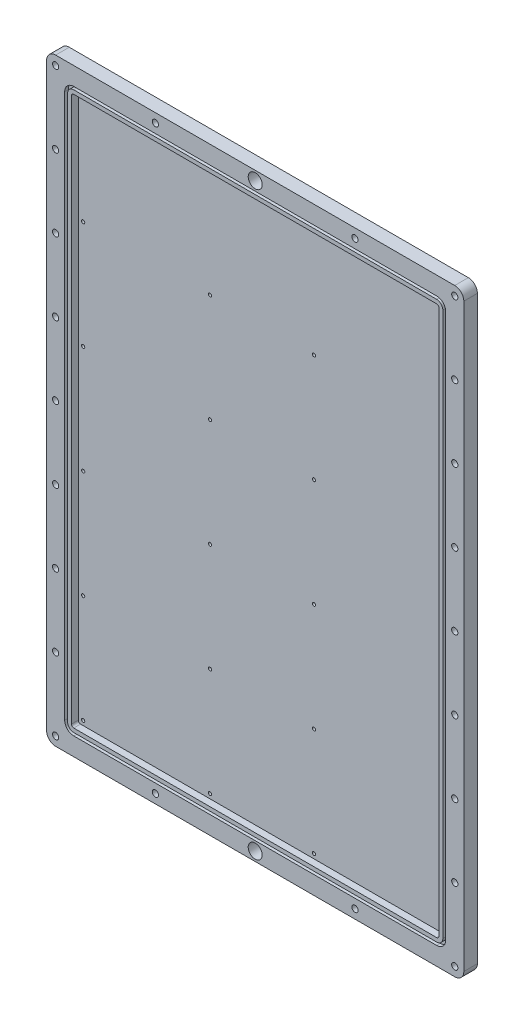
SolidWorks part; units mm, degrees
ref_plane "Front Plane" through (0, 0, 0) normal (0, 0, 1) x (1, 0, 0)
ref_plane "Top Plane" through (0, 0, 0) normal (0, 1, 0) x (1, 0, 0)
ref_plane "Right Plane" through (0, 0, 0) normal (1, 0, 0) x (0, 0, -1)
sketch "Sketch1" plane through (0, 0, 0) normal (0, 0, 1) x (1, 0, 0)
  line L1 (0, 0) -> (292.0492, 0)
  line L2 (0, 0) -> (0, 419.0492)
  line L3 (0, 419.0492) -> (292.0492, 419.0492)
  line L4 (292.0492, 0) -> (292.0492, 419.0492)
  dimension "D1" = 419.0492
  dimension "D2" = 292.0492
extrude "Boss-Extrude1" add sketch "Sketch1" along normal blind 9.525
sketch "Sketch4" plane through (0, 0, 9.525) normal (0, 0, 1) x (1, 0, 0)
  line L0 (91.477, 6.3246) -> (91.477, 0) construction
  line L1 (0, 0) -> (292.0492, 0) construction
  line L2 (6.3246, 94.9672) -> (0, 94.9672) construction
  line L4 (6.3246, 412.7246) -> (285.7246, 412.7246) construction
  line L5 (6.3246, 412.7246) -> (6.3246, 6.3246) construction
  line L6 (6.3246, 6.3246) -> (285.7246, 6.3246) construction
  line L7 (285.7246, 412.7246) -> (285.7246, 6.3246) construction
  line L11 (0, 419.0492) -> (0, 0) construction
  line L12 (285.7246, 110.613) -> (292.0492, 110.613) construction
  line L13 (292.0492, 0) -> (292.0492, 419.0492) construction
  line L14 (125.5626, 412.7246) -> (125.5626, 419.0492) construction
  line L15 (292.0492, 419.0492) -> (0, 419.0492) construction
  circle A0 centre (6.3246, 6.3246) radius 2.1844
  circle A1 centre (6.3246, 412.7246) radius 2.1844
  circle A2 centre (285.7246, 412.7246) radius 2.1844
  circle A3 centre (285.7246, 6.3246) radius 2.1844
  dimension "D5" = 4.3688
  dimension "D1" = 279.4
  dimension "D2" = 406.4
extrude "Cut-Extrude1" cut sketch "Sketch4" against normal through all
sketch "Sketch5" plane through (0, 0, 9.525) normal (0, 0, 1) x (1, 0, 0)
  line L0 (0, 209.5246) -> (12.6746, 209.5246) construction
  line L1 (19.0246, 406.3746) -> (273.0246, 406.3746)
  line L2 (12.6746, 400.0246) -> (12.6746, 19.0246)
  line L3 (19.0246, 12.6746) -> (273.0246, 12.6746)
  line L4 (279.3746, 400.0246) -> (279.3746, 19.0246)
  line L5 (0, 419.0492) -> (0, 0) construction
  line L6 (279.3746, 209.5246) -> (292.0492, 209.5246) construction
  line L8 (19.0246, 14.7066) -> (273.0246, 14.7066)
  line L9 (14.7066, 400.0246) -> (14.7066, 19.0246)
  line L10 (19.0246, 404.3426) -> (273.0246, 404.3426)
  line L11 (277.3426, 400.0246) -> (277.3426, 19.0246)
  line L12 (292.0492, 0) -> (292.0492, 419.0492) construction
  line L13 (146.0246, 12.6746) -> (146.0246, 0) construction
  line L14 (0, 0) -> (292.0492, 0) construction
  line L15 (146.0246, 406.3746) -> (146.0246, 419.0492) construction
  line L16 (292.0492, 419.0492) -> (0, 419.0492) construction
  arc A0 (273.0246, 12.6746) -> (279.3746, 19.0246) centre (273.0246, 19.0246) ccw
  arc A1 (12.6746, 19.0246) -> (19.0246, 12.6746) centre (19.0246, 19.0246) ccw
  arc A2 (273.0246, 406.3746) -> (279.3746, 400.0246) centre (273.0246, 400.0246) cw
  arc A3 (19.0246, 406.3746) -> (12.6746, 400.0246) centre (19.0246, 400.0246) ccw
  arc A4 (14.7066, 19.0246) -> (19.0246, 14.7066) centre (19.0246, 19.0246) ccw
  arc A5 (19.0246, 404.3426) -> (14.7066, 400.0246) centre (19.0246, 400.0246) ccw
  arc A6 (273.0246, 404.3426) -> (277.3426, 400.0246) centre (273.0246, 400.0246) cw
  arc A7 (273.0246, 14.7066) -> (277.3426, 19.0246) centre (273.0246, 19.0246) ccw
  dimension "D5" = 6.35
  dimension "D1" = 266.7
  dimension "D2" = 393.7
  dimension "D6" = 2.032
  dimension "D7" = 2.032
extrude "Cut-Extrude2" cut sketch "Sketch5" against normal blind 2.54 contours L1 A3 L2 A1 L3 A0 L4 A2 A7 L8 A4 L9 A5 L10 A6 L11 region at (146.0246, 405.8991, 9.525)
pattern_linear "LPattern3" count 4 spacing 69.85 along (1, 0, 0) of face at (8.509, 412.7246, 0) of face at (8.509, 6.3246, 0)
pattern_linear "LPattern4" count 8 spacing 50.8 along (0, -1, 0) of face at (8.509, 412.7246, 0) of face at (287.909, 412.7246, 0)
sketch "Sketch6" plane through (0, 0, 9.525) normal (0, 0, 1) x (1, 0, 0)
  line L4 (274.6121, 19.0246) -> (274.6121, 400.0246)
  line L5 (274.6121, 19.0246) -> (274.6121, 400.0246)
  line L6 (273.0246, 401.6121) -> (19.0246, 401.6121)
  line L7 (273.0246, 401.6121) -> (19.0246, 401.6121)
  line L8 (17.4371, 400.0246) -> (17.4371, 19.0246)
  line L9 (17.4371, 400.0246) -> (17.4371, 19.0246)
  line L10 (19.0246, 17.4371) -> (273.0246, 17.4371)
  line L11 (19.0246, 17.4371) -> (273.0246, 17.4371)
  arc A4 (273.0246, 17.4371) -> (274.6121, 19.0246) centre (273.0246, 19.0246) ccw
  arc A5 (273.0246, 17.4371) -> (274.6121, 19.0246) centre (273.0246, 19.0246) ccw
  arc A6 (274.6121, 400.0246) -> (273.0246, 401.6121) centre (273.0246, 400.0246) ccw
  arc A7 (274.6121, 400.0246) -> (273.0246, 401.6121) centre (273.0246, 400.0246) ccw
  arc A8 (19.0246, 401.6121) -> (17.4371, 400.0246) centre (19.0246, 400.0246) ccw
  arc A9 (19.0246, 401.6121) -> (17.4371, 400.0246) centre (19.0246, 400.0246) ccw
  arc A10 (17.4371, 19.0246) -> (19.0246, 17.4371) centre (19.0246, 19.0246) ccw
  arc A11 (17.4371, 19.0246) -> (19.0246, 17.4371) centre (19.0246, 19.0246) ccw
  dimension "D1" = 2.7305
extrude "Cut-Extrude3" cut sketch "Sketch6" against normal blind 4.7625
sketch "Sketch7" plane through (0, 0, 4.7625) normal (0, 0, 1) x (1, 0, 0)
  line L0 (273.0246, 401.6121) -> (19.0246, 401.6121) construction
  line L1 (20.8407, 398.4371) -> (271.2085, 398.4371) construction
  line L2 (20.8407, 398.4371) -> (20.8407, 20.6121) construction
  line L3 (20.8407, 20.6121) -> (271.2085, 20.6121) construction
  line L4 (271.2085, 398.4371) -> (271.2085, 20.6121) construction
  line L5 (17.4371, 400.0246) -> (17.4371, 19.0246) construction
  line L6 (274.6121, 19.0246) -> (274.6121, 400.0246) construction
  line L7 (19.0246, 17.4371) -> (273.0246, 17.4371) construction
  line L8 (17.4371, 400.0246) -> (17.4371, 19.0246) construction
  line L9 (274.6121, 19.0246) -> (274.6121, 400.0246) construction
  circle A0 centre (20.8407, 398.4371) radius 1.1303
  circle A1 centre (271.2085, 398.4371) radius 1.1303
  circle A2 centre (20.8407, 20.6121) radius 1.1303
  circle A3 centre (109.6391, 20.6121) radius 1.1303
  circle A4 centre (109.6391, 398.4371) radius 1.1303
  circle A5 centre (182.4101, 398.4371) radius 1.1303
  circle A6 centre (182.4101, 20.6121) radius 1.1303
  circle A7 centre (271.2085, 20.6121) radius 1.1303
  dimension "D5" = 2.2606
  dimension "D1" = 3.175
  dimension "D2" = 3.4036
  dimension "D3" = 3.4036
  dimension "D4" = 3.175
  dimension "D6" = 92.202
  dimension "D7" = 92.202
  dimension "D8" = 88.7984
  dimension "D9" = 88.7984
extrude "Cut-Extrude4" cut sketch "Sketch7" against normal blind 3.175
sketch "Sketch8" plane through (0, 0, 9.525) normal (0, 0, 1) x (1, 0, 0)
  circle A0 centre (146.0246, 412.7246) radius 4.9022
  circle A1 centre (146.0246, 6.3246) radius 4.9022
  dimension "D1" = 9.8044
extrude "Cut-Extrude5" cut sketch "Sketch8" against normal through all
fillet "Fillet1" radius 6.35 4 edges at (292.0492, 0, 4.7625) (0, 0, 4.7625) (292.0492, 419.0492, 4.7625) (0, 419.0492, 4.7625)
pattern_linear "LPattern10" count 5 spacing 75.565 along (0, -1, 0) of "Cut-Extrude4"
chamfer "Chamfer1" distance 2.8448 angle 41 22 edges at (78.359, 412.7246, 0) (218.059, 412.7246, 0) (287.909, 412.7246, 0) (287.909, 361.9246, 0) (287.909, 311.1246, 0) (287.909, 260.3246, 0) (287.909, 209.5246, 0) (287.909, 158.7246, 0) (287.909, 107.9246, 0) (287.909, 57.1246, 0) (287.909, 6.3246, 0) (218.059, 6.3246, 0) (78.359, 6.3246, 0) (8.509, 6.3246, 0) (8.509, 57.1246, 0) (8.509, 107.9246, 0) (8.509, 158.7246, 0) (8.509, 260.3246, 0) (8.509, 311.1246, 0) (8.509, 412.7246, 0) (8.509, 361.9246, 0) (8.509, 209.5246, 0) first distance on face at (78.359, 412.7246, 0) first distance on face at (218.059, 412.7246, 0) first distance on face at (287.909, 412.7246, 0) first distance on face at (287.909, 361.9246, 0) first distance on face at (287.909, 311.1246, 0) first distance on face at (287.909, 260.3246, 0) first distance on face at (287.909, 209.5246, 0) first distance on face at (287.909, 158.7246, 0) first distance on face at (287.909, 107.9246, 0) first distance on face at (287.909, 57.1246, 0) first distance on face at (287.909, 6.3246, 0) first distance on face at (218.059, 6.3246, 0) first distance on face at (78.359, 6.3246, 0) first distance on face at (8.509, 6.3246, 0) first distance on face at (8.509, 57.1246, 0) first distance on face at (8.509, 107.9246, 0) first distance on face at (8.509, 158.7246, 0) first distance on face at (8.509, 260.3246, 0) first distance on face at (8.509, 311.1246, 0) first distance on face at (8.509, 412.7246, 0) first distance on face at (8.509, 361.9246, 0) first distance on face at (8.509, 209.5246, 0)
